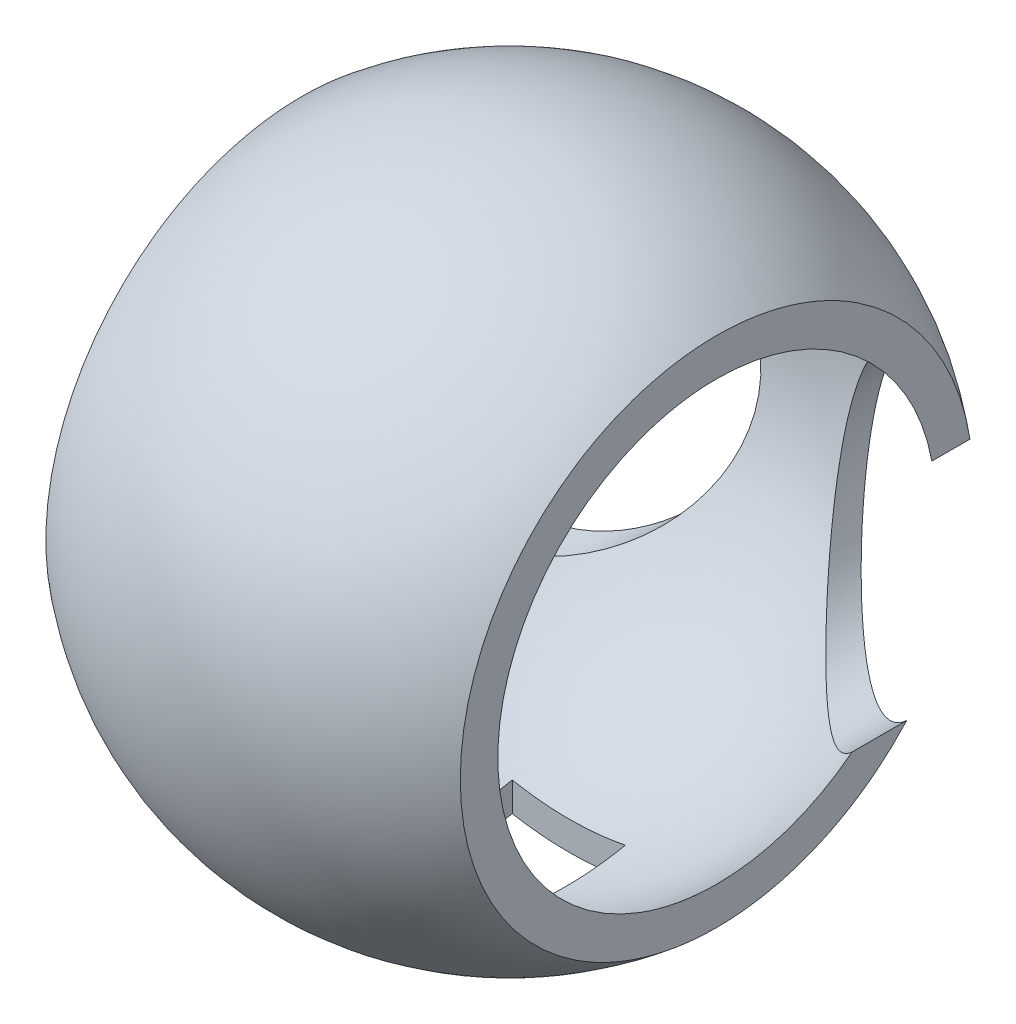
SolidWorks part; units mm, degrees
ref_plane "Alzado" through (0, 0, 0) normal (0, 0, 1) x (1, 0, 0)
ref_plane "Planta" through (0, 0, 0) normal (0, 1, 0) x (1, 0, 0)
ref_plane "Vista lateral" through (0, 0, 0) normal (1, 0, 0) x (0, 0, -1)
sketch "Croquis1" plane through (0, 0, 0) normal (0, 0, 1) x (1, 0, 0)
  line L0 (0, 35) -> (0, -35)
  arc A0 (0, -35) -> (0, 35) centre (0, 0) ccw
revolve "Revolución1" add sketch "Croquis1" angle 360 about L0
sketch "Croquis2" plane through (0, 0, 0) normal (0, 0, 1) x (1, 0, 0)
  line L0 (-35, 0) -> (-22, 0)
  line L1 (35, 0) -> (22, 0)
  line L3 (-22, -30.7026) -> (-36.5258, -30.7026)
  line L4 (-22, -30.7026) -> (-22, 29.2099)
  line L5 (-22, 29.2099) -> (-36.5258, 29.2099)
  line L6 (-36.5258, -30.7026) -> (-36.5258, 29.2099)
  line L7 (22, -30.7026) -> (35, -30.7026)
  line L8 (22, -30.7026) -> (22, 29.2099)
  line L9 (22, 29.2099) -> (35, 29.2099)
  line L10 (35, -30.7026) -> (35, 29.2099)
  circle A0 centre (0, 0) radius 35 construction
extrude "Cortar-Extruir1" cut sketch "Croquis2" against normal blind 29 and the other way blind 29 contours L6 L3 L4 L5 | L1 L10 L9 L8 | L7 L10 L1 L8 region at (28.5, -15.3513, 0) region at (28.5, 14.605, 0) region at (-29.2629, -0.7464, 0)
shell "Vaciado2" thickness 3 removed face at (22, 0, 27.2213) removed face at (-22, 0, 27.2213)
sketch "Croquis3" plane through (0, 0, 0) normal (0, 0, 1) x (1, 0, 0)
  ellipse E0 centre (-15.4574, -7.0522) end of major axis (-15.4574, 6.9478) minor radius 11
  ellipse E1 centre (15.4574, -7.013) end of major axis (15.4574, -21.013) minor radius 11
extrude "Cortar-Extruir2" cut sketch "Croquis3" against normal blind 36
sketch "Croquis4" plane through (0, 0, 0) normal (0, 1, 0) x (1, 0, 0)
  line L1 (0, 0) -> (0, -15.6)
  line L2 (0, 0) -> (0, 8)
  line L3 (0, 6.297) -> (-6, 6.297)
  line L5 (-6, 6.297) -> (6, 6.297)
  line L6 (-6, 6.297) -> (-6, -15.6)
  line L7 (-6, -15.6) -> (6, -15.6)
  line L8 (6, 6.297) -> (6, -15.6)
  point P0 (0, 0)
extrude "Cortar-Extruir5" cut sketch "Croquis4" against normal blind 40 contours L6 L7 L1 L2 L3 | L8 L5 L2 L1 L7 region at (3, 0, 4.6515) region at (-3, 0, 4.6515)
